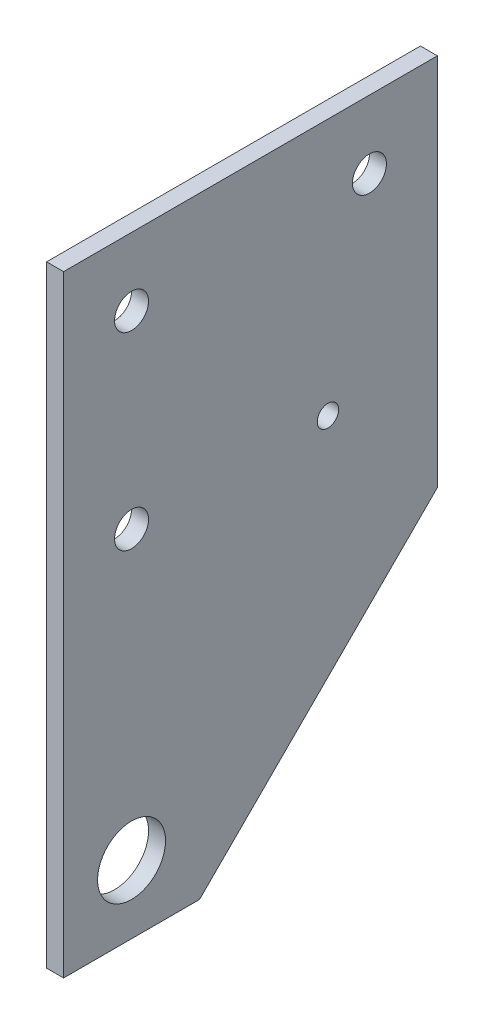
SolidWorks part; units mm, degrees
ref_plane "Front Plane" through (0, 0, 0) normal (0, 0, 1) x (1, 0, 0)
ref_plane "Top Plane" through (0, 0, 0) normal (0, 1, 0) x (1, 0, 0)
ref_plane "Right Plane" through (0, 0, 0) normal (1, 0, 0) x (0, 0, -1)
sketch "Sketch1" plane through (0, 0, 0) normal (1, 0, 0) x (0, 0, -1)
  line L0 (-12.7, 101.6) -> (57.15, 101.6)
  line L1 (12.7, -12.7) -> (57.15, 31.75)
  line L2 (57.15, 31.75) -> (57.15, 101.6)
  line L4 (-12.7, -12.7) -> (12.7, -12.7)
  line L6 (-12.7, 101.6) -> (-12.7, -12.7)
  circle A0 centre (36.6958, 53.601) radius 2
  circle A1 centre (36.6958, 53.601) radius 2 construction
  circle A2 centre (0, 0) radius 6.35
  circle A3 centre (0, 0) radius 61.595 construction
  circle A4 centre (0, 88.9) radius 3.175
  circle A5 centre (44.45, 88.9) radius 3.175
  circle A6 centre (0, 53.601) radius 3.175
  point P11 (0, -12.7)
  dimension "D4" = 69.85
  dimension "D6" = 12.7
  dimension "D8" = 123.19
  dimension "D9" = 6.35
  dimension "D11" = 12.7
  dimension "D12" = 12.7
  dimension "D7" = 6.35
  dimension "D14" = 6.35
  dimension "D1" = 25.4
  dimension "D2" = 69.85
  dimension "D3" = 114.3
  dimension "D5" = 12.7
  dimension "D10" = 12.7
  dimension "D13" = 12.7
extrude "Boss-Extrude1" add sketch "Sketch1" along normal blind 3.175
